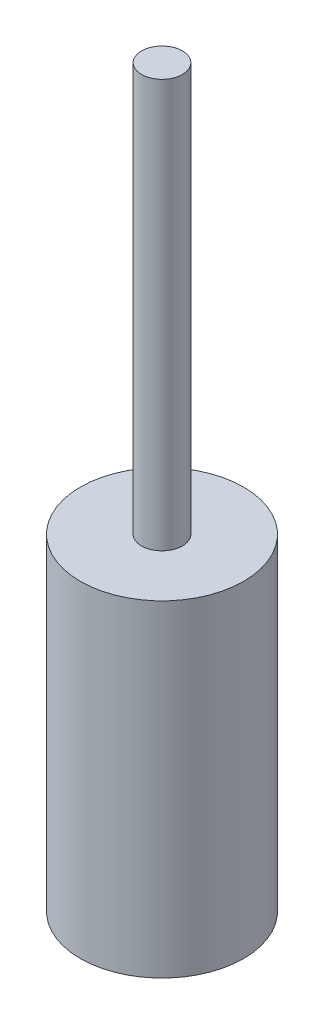
SolidWorks part; units mm, degrees
ref_plane "Front Plane" through (0, 0, 0) normal (0, 0, 1) x (1, 0, 0)
ref_plane "Top Plane" through (0, 0, 0) normal (0, 1, 0) x (1, 0, 0)
ref_plane "Right Plane" through (0, 0, 0) normal (1, 0, 0) x (0, 0, -1)
sketch "Sketch2" plane through (0, 0, 0) normal (0, 1, 0) x (1, 0, 0)
  circle A0 centre (0, 0) radius 10
  circle A1 centre (0, 0) radius 2.5
  dimension "D1" = 20
  dimension "D2" = 5
extrude "Boss-Extrude1" add sketch "Sketch2" along normal blind 40 contours A1 | A0 A1 region at (-9.7172, 0, 0) region at (0, 0, 0)
extrude "Boss-Extrude2" add sketch "Sketch2<3>" along normal blind 50 from surface contours A1 region at (0, 0, 0) starting at face at (0, 40, 10)
sketch "Sketch2<3>" plane through (0, 0, 0) normal (0, 1, 0) x (1, 0, 0) same geometry as "Sketch2"
sketch "Sketch3" plane through (0, 0, 0) normal (0, 1, 0) x (1, 0, 0)
  circle A0 centre (0, 0) radius 5
  dimension "D1" = 10
extrude "Cut-Extrude1" cut sketch "Sketch3" along normal blind 20 contours A0 region at (0, 0, 0)
